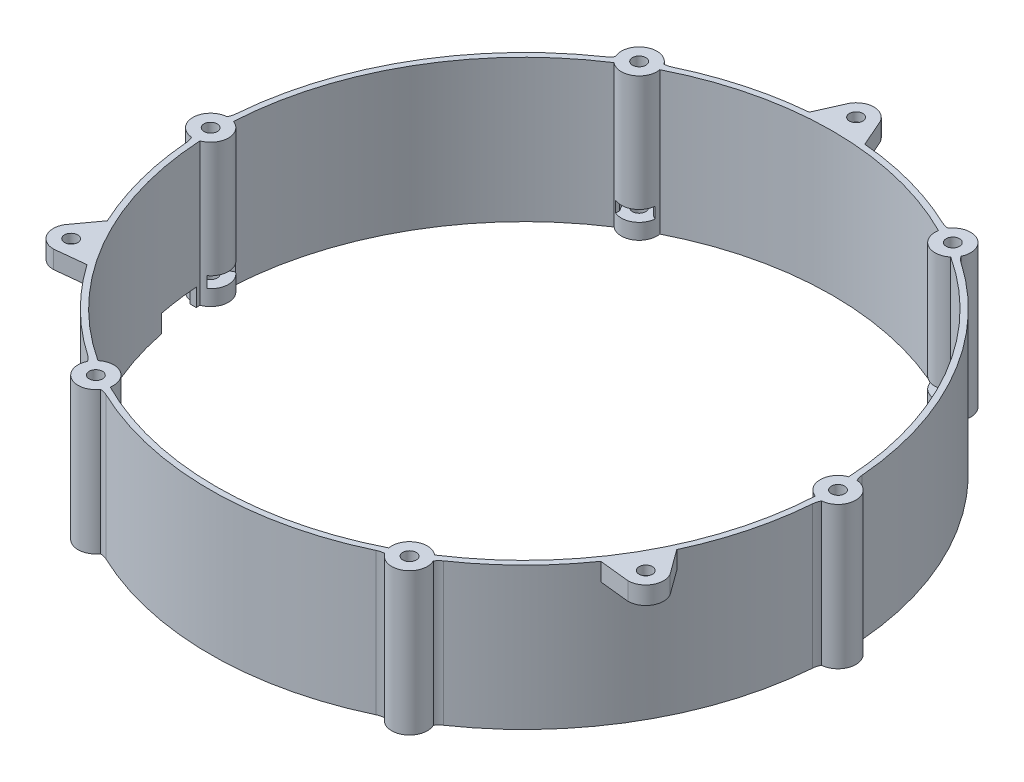
SolidWorks part; units mm, degrees
ref_plane "前视基准面" through (0, 0, 0) normal (0, 0, 1) x (1, 0, 0)
ref_plane "上视基准面" through (0, 0, 0) normal (0, 1, 0) x (1, 0, 0)
ref_plane "右视基准面" through (0, 0, 0) normal (1, 0, 0) x (0, 0, -1)
sketch "草图1" plane through (0, 0, 0) normal (0, 1, 0) x (1, 0, 0)
  line L12 (-35.25, -61.0548) -> (0, 0) construction
  line L13 (-67.3629, 4.3002) -> (-9.579, 4.3002)
  line L14 (-67.3629, -4.3002) -> (-9.579, -4.3002)
  line L15 (9.579, 4.3002) -> (67.3629, 4.3002)
  line L16 (9.579, -4.3002) -> (67.3629, -4.3002)
  line L17 (1.0654, -10.4458) -> (29.9573, -60.4881)
  line L18 (8.5136, -6.1456) -> (37.4056, -56.1878)
  line L19 (-29.9573, 60.4881) -> (-1.0654, 10.4458)
  line L20 (-37.4056, 56.1878) -> (-8.5136, 6.1456)
  line L21 (-8.5136, -6.1456) -> (-37.4056, -56.1878)
  line L22 (-1.0654, -10.4458) -> (-29.9573, -60.4881)
  line L23 (37.4056, 56.1878) -> (8.5136, 6.1456)
  line L24 (29.9573, 60.4881) -> (1.0654, 10.4458)
  line L25 (-9.579, 4.3002) -> (-67.3629, 4.3002)
  line L26 (-9.579, -4.3002) -> (-67.3629, -4.3002)
  line L27 (67.3629, -4.3002) -> (9.579, -4.3002)
  line L28 (67.3629, 4.3002) -> (9.579, 4.3002)
  line L29 (-1.0654, 10.4458) -> (-29.9573, 60.4881)
  line L30 (-8.5136, 6.1456) -> (-37.4056, 56.1878)
  line L31 (29.9573, -60.4881) -> (1.0654, -10.4458)
  line L32 (37.4056, -56.1878) -> (8.5136, -6.1456)
  line L33 (8.5136, 6.1456) -> (37.4056, 56.1878)
  line L34 (1.0654, 10.4458) -> (29.9573, 60.4881)
  line L35 (-37.4056, -56.1878) -> (-8.5136, -6.1456)
  line L36 (-29.9573, -60.4881) -> (-1.0654, -10.4458)
  line L37 (10.5, 0) -> (70.5, 0) construction
  line L38 (-10.5, 0) -> (9.5, 0) construction
  line L47 (-31.5, -54.5596) -> (-6.5, -11.2583) construction
  line L48 (-32.799, -53.8096) -> (-7.799, -10.5083)
  line L49 (-30.201, -55.3096) -> (-5.201, -12.0083)
  line L50 (-63, 0) -> (-13, 0) construction
  line L51 (-63, 1.5) -> (-13, 1.5)
  line L52 (-63, -1.5) -> (-13, -1.5)
  line L53 (-31.5, 54.5596) -> (-6.5, 11.2583) construction
  line L54 (-30.201, 55.3096) -> (-5.201, 12.0083)
  line L55 (-32.799, 53.8096) -> (-7.799, 10.5083)
  line L56 (31.5, 54.5596) -> (6.5, 11.2583) construction
  line L57 (32.799, 53.8096) -> (7.799, 10.5083)
  line L58 (30.201, 55.3096) -> (5.201, 12.0083)
  line L59 (63, 0) -> (13, 0) construction
  line L60 (63, -1.5) -> (13, -1.5)
  line L61 (63, 1.5) -> (13, 1.5)
  line L62 (31.5, -54.5596) -> (6.5, -11.2583) construction
  line L63 (30.201, -55.3096) -> (5.201, -12.0083)
  line L64 (32.799, -53.8096) -> (7.799, -10.5083)
  arc A0 (-7.8594, 1.4934) -> (-7.8594, -1.4934) centre (0, 0) ccw construction
  circle A1 centre (-8, 0) radius 1.5
  circle A2 centre (0, 8) radius 1.5
  circle A3 centre (8, 0) radius 1.5
  circle A4 centre (0, -8) radius 1.5
  arc A5 (-8.5136, 6.1456) -> (-9.579, 4.3002) centre (0, 0) ccw
  arc A6 (-67.3629, -4.3002) -> (-37.4056, -56.1878) centre (0, 0) ccw
  arc A7 (-70.5, 3) -> (-70.5, -3) centre (-70.5, 0) ccw
  circle A8 centre (-70.5, 0) radius 1.5
  arc A9 (-32.6519, 62.5548) -> (-37.8481, 59.5548) centre (-35.25, 61.0548) ccw
  circle A10 centre (-35.25, 61.0548) radius 1.5
  arc A11 (37.8481, 59.5548) -> (32.6519, 62.5548) centre (35.25, 61.0548) ccw
  circle A12 centre (35.25, 61.0548) radius 1.5
  arc A13 (70.5, -3) -> (70.5, 3) centre (70.5, 0) ccw
  circle A14 centre (70.5, 0) radius 1.5
  arc A15 (32.6519, -62.5548) -> (37.8481, -59.5548) centre (35.25, -61.0548) ccw
  circle A16 centre (35.25, -61.0548) radius 1.5
  arc A17 (-37.8481, -59.5548) -> (-32.6519, -62.5548) centre (-35.25, -61.0548) ccw
  circle A18 centre (-35.25, -61.0548) radius 1.5
  arc A21 (1.4934, 7.8594) -> (-6.746, 4.3002) centre (0, 0) ccw construction
  arc A22 (-1.4934, -7.8594) -> (1.4934, -7.8594) centre (0, 0) ccw construction
  arc A23 (7.8594, -1.4934) -> (6.746, 4.3002) centre (0, 0) ccw construction
  circle A24 centre (0, 0) radius 4.5
  arc A25 (1.0654, 10.4458) -> (-1.0654, 10.4458) centre (0, 0) ccw
  arc A26 (9.579, 4.3002) -> (8.5136, 6.1456) centre (0, 0) ccw
  arc A27 (8.5136, -6.1456) -> (9.579, -4.3002) centre (0, 0) ccw
  arc A28 (-1.0654, -10.4458) -> (1.0654, -10.4458) centre (0, 0) ccw
  arc A29 (-9.579, -4.3002) -> (-8.5136, -6.1456) centre (0, 0) ccw
  arc A30 (-37.4056, 56.1878) -> (-67.3629, 4.3002) centre (0, 0) ccw
  arc A31 (29.9573, 60.4881) -> (-29.9573, 60.4881) centre (0, 0) ccw
  arc A32 (67.3629, 4.3002) -> (37.4056, 56.1878) centre (0, 0) ccw
  arc A33 (37.4056, -56.1878) -> (67.3629, -4.3002) centre (0, 0) ccw
  arc A34 (-29.9573, -60.4881) -> (29.9573, -60.4881) centre (0, 0) ccw
  arc A35 (32.6519, 62.5548) -> (-32.6519, 62.5548) centre (0, 0) ccw
  arc A36 (70.5, 3) -> (37.8481, 59.5548) centre (0, 0) ccw
  arc A37 (37.8481, -59.5548) -> (70.5, -3) centre (0, 0) ccw
  arc A38 (-32.6519, -62.5548) -> (32.6519, -62.5548) centre (0, 0) ccw
  arc A39 (-70.5, -3) -> (-37.8481, -59.5548) centre (0, 0) ccw
  arc A40 (-37.8481, 59.5548) -> (-70.5, 3) centre (0, 0) ccw
  arc A41 (-32.799, -53.8096) -> (-30.201, -55.3096) centre (-31.5, -54.5596) ccw
  arc A42 (-5.201, -12.0083) -> (-7.799, -10.5083) centre (-6.5, -11.2583) ccw
  arc A43 (-63, 1.5) -> (-63, -1.5) centre (-63, 0) ccw
  arc A44 (-13, -1.5) -> (-13, 1.5) centre (-13, 0) ccw
  arc A45 (-30.201, 55.3096) -> (-32.799, 53.8096) centre (-31.5, 54.5596) ccw
  arc A46 (-7.799, 10.5083) -> (-5.201, 12.0083) centre (-6.5, 11.2583) ccw
  arc A47 (32.799, 53.8096) -> (30.201, 55.3096) centre (31.5, 54.5596) ccw
  arc A48 (5.201, 12.0083) -> (7.799, 10.5083) centre (6.5, 11.2583) ccw
  arc A49 (63, -1.5) -> (63, 1.5) centre (63, 0) ccw
  arc A50 (13, 1.5) -> (13, -1.5) centre (13, 0) ccw
  arc A51 (30.201, -55.3096) -> (32.799, -53.8096) centre (31.5, -54.5596) ccw
  arc A52 (7.799, -10.5083) -> (5.201, -12.0083) centre (6.5, -11.2583) ccw
  point P14 (0, 0)
  point P15 (0, 0)
  point P20 (-19, -32.909)
  point P51 (-38, 0)
  point P52 (0, 0)
  point P92 (-19, 32.909)
  point P99 (19, 32.909)
  point P106 (38, 0)
  point P111 (0, 0)
  point P130 (19, -32.909)
  point P135 (0, 0)
  dimension "D1" = 16
  dimension "D2" = 3
  dimension "D4" = 2.5
  dimension "D5" = 135
  dimension "D6" = 6
  dimension "D7" = 3
  dimension "D9" = 9
  dimension "D11" = 50
  dimension "D8" = 6
  dimension "D12" = 13
  dimension "D13" = 3
  dimension "D3" = 4
  dimension "D10" = 6
  dimension "D14" = 6
extrude "凸台-拉伸1" add sketch "草图1" along normal blind 4 contours A9 A40 A7 A39 A17 A38 A15 A37 A13 A36 A11 A35 A52 L64 A51 L63 A50 L61 A49 L60 A48 L58 A47 L57 A46 L55 A45 L54 A44 L52 A43 L51 A42 L49 A41 L48 L14 A29 L21 A6 A1 A2 region at (-59.3453, 0, -34.263)
fillet "圆角1" radius 4 24 edges at (-37.4056, 2, 56.1878) (-67.3629, 2, 4.3002) (-70.5, 2, 3) (-70.5, 2, -3) (-67.3629, 2, -4.3002) (-37.4056, 2, -56.1878) (-29.9573, 2, -60.4881) (-37.8481, 2, -59.5548) (-32.6519, 2, -62.5548) (32.6519, 2, -62.5548) (29.9573, 2, -60.4881) (37.4056, 2, -56.1878) (37.8481, 2, -59.5548) (70.5, 2, -3) (70.5, 2, 3) (67.3629, 2, -4.3002) (67.3629, 2, 4.3002) (37.8481, 2, 59.5548) (37.4056, 2, 56.1878) (32.6519, 2, 62.5548) (29.9573, 2, 60.4881) (-37.8481, 2, 59.5548) (-29.9573, 2, 60.4881) (-32.6519, 2, 62.5548)
fillet "圆角2" radius 4 12 edges at (-1.0654, 2, 10.4458) (-8.5136, 2, 6.1456) (-9.579, 2, 4.3002) (-9.579, 2, -4.3002) (-8.5136, 2, -6.1456) (1.0654, 2, -10.4458) (-1.0654, 2, -10.4458) (9.579, 2, -4.3002) (8.5136, 2, -6.1456) (9.579, 2, 4.3002) (8.5136, 2, 6.1456) (1.0654, 2, 10.4458)
sketch "草图2" plane through (0, 0, 0) normal (0, -1, 0) x (-1, 0, 0)
  line L0 (23.0864, -63.4293) -> (23.5994, -64.8388)
  line L1 (0, 0) -> (0, -46.6688) construction
  line L2 (-23.0864, -63.4293) -> (-23.5994, -64.8388)
  line L3 (-43.3882, -51.708) -> (-44.3523, -52.8571)
  line L4 (-66.4745, -11.7213) -> (-67.9517, -11.9817)
  line L5 (-66.4745, 11.7213) -> (-67.9517, 11.9817)
  line L6 (-43.3882, 51.708) -> (-44.3523, 52.8571)
  line L7 (-23.0864, 63.4293) -> (-23.5994, 64.8388)
  line L8 (23.0864, 63.4293) -> (23.5994, 64.8388)
  line L9 (43.3882, 51.708) -> (44.3523, 52.8571)
  line L10 (66.4745, 11.7213) -> (67.9517, 11.9817)
  line L11 (66.4745, -11.7213) -> (67.9517, -11.9817)
  line L12 (43.3882, -51.708) -> (44.3523, -52.8571)
  arc A0 (-23.0864, -63.4293) -> (23.0864, -63.4293) centre (0, 0) ccw
  arc A1 (-23.5994, -64.8388) -> (23.5994, -64.8388) centre (0, 0) ccw
  arc A2 (-66.4745, -11.7213) -> (-43.3882, -51.708) centre (0, 0) ccw
  arc A3 (-67.9517, -11.9817) -> (-44.3523, -52.8571) centre (0, 0) ccw
  arc A4 (-43.3882, 51.708) -> (-66.4745, 11.7213) centre (0, 0) ccw
  arc A5 (-44.3523, 52.8571) -> (-67.9517, 11.9817) centre (0, 0) ccw
  arc A6 (23.0864, 63.4293) -> (-23.0864, 63.4293) centre (0, 0) ccw
  arc A7 (23.5994, 64.8388) -> (-23.5994, 64.8388) centre (0, 0) ccw
  arc A8 (66.4745, 11.7213) -> (43.3882, 51.708) centre (0, 0) ccw
  arc A9 (67.9517, 11.9817) -> (44.3523, 52.8571) centre (0, 0) ccw
  arc A10 (43.3882, -51.708) -> (66.4745, -11.7213) centre (0, 0) ccw
  arc A11 (44.3523, -52.8571) -> (67.9517, -11.9817) centre (0, 0) ccw
  point P30 (0, 0)
  dimension "D1" = 1.5
  dimension "D2" = 20
  dimension "D3" = 6
extrude "凸台-拉伸2" add sketch "草图2" along normal blind 5
chamfer "倒角1" distance 0.5 angle 45 6 edges at (59.7558, -5, -34.5) (59.7558, -5, 34.5) (0, -5, 69) (-59.7558, -5, 34.5) (-59.7558, -5, -34.5) (0, -5, -69)
sketch "草图3" plane through (0, 0, 0) normal (0, -1, 0) x (1, 0, 0)
  arc A0 (-37.8339, 58.0014) -> (-69.1476, 3.7644) centre (0, 0) ccw
  arc A2 (-69.1476, -3.7644) -> (-37.8339, -58.0014) centre (0, 0) ccw
  arc A4 (69.1476, 3.7644) -> (69.1476, -3.7644) centre (70.5, 0) ccw
  arc A5 (69.1476, 3.7644) -> (37.8339, 58.0014) centre (0, 0) ccw
  arc A6 (37.8339, -58.0014) -> (69.1476, -3.7644) centre (0, 0) ccw
  arc A7 (-31.3137, -61.7658) -> (31.3137, -61.7658) centre (0, 0) ccw
  arc A9 (70.7964, -3.989) -> (70.7964, 3.989) centre (70.5, 0) ccw
  arc A10 (31.3137, 61.7658) -> (37.8339, 58.0014) centre (35.25, 61.0548) ccw
  arc A11 (31.3137, 61.7658) -> (-31.3137, 61.7658) centre (0, 0) ccw
  arc A12 (37.8339, -58.0014) -> (31.3137, -61.7658) centre (35.25, -61.0548) ccw
  arc A13 (-38.8528, -59.317) -> (-31.9436, -63.306) centre (-35.25, -61.0548) ccw
  arc A14 (-70.7964, 3.989) -> (-70.7964, -3.989) centre (-70.5, 0) ccw
  arc A15 (-31.9436, 63.306) -> (-38.8528, 59.317) centre (-35.25, 61.0548) ccw
  arc A16 (38.8528, 59.317) -> (31.9436, 63.306) centre (35.25, 61.0548) ccw
  arc A17 (-37.8339, 58.0014) -> (-31.3137, 61.7658) centre (-35.25, 61.0548) ccw
  arc A18 (-69.1476, -3.7644) -> (-69.1476, 3.7644) centre (-70.5, 0) ccw
  arc A19 (-31.3137, -61.7658) -> (-37.8339, -58.0014) centre (-35.25, -61.0548) ccw
  arc A20 (31.9436, -63.306) -> (38.8528, -59.317) centre (35.25, -61.0548) ccw
  circle A21 centre (70.5, 0) radius 1.5
  circle A22 centre (35.25, 61.0548) radius 1.5
  circle A23 centre (-35.25, 61.0548) radius 1.5
  arc A24 (-38.2453, -61.2225) -> (-33.8976, -63.7327) centre (-35.25, -61.0548) ccw
  arc A25 (-30.3726, -63.6926) -> (-33.8976, -63.7327) centre (-32.0944, -67.3031) ccw
  arc A26 (-30.3726, -63.6926) -> (30.3726, -63.6926) centre (0, 0) ccw
  arc A27 (33.8976, -63.7327) -> (30.3726, -63.6926) centre (32.0944, -67.3031) ccw
  arc A28 (33.8976, -63.7327) -> (38.2453, -61.2225) centre (35.25, -61.0548) ccw
  arc A29 (39.9731, -58.1498) -> (38.2453, -61.2225) centre (42.2391, -61.4461) ccw
  arc A30 (39.9731, -58.1498) -> (70.3458, -5.5428) centre (0, 0) ccw
  arc A31 (72.1429, -2.5102) -> (70.3458, -5.5428) centre (74.3334, -5.857) ccw
  arc A32 (72.1429, -2.5102) -> (72.1429, 2.5102) centre (70.5, 0) ccw
  arc A33 (70.3458, 5.5428) -> (72.1429, 2.5102) centre (74.3334, 5.857) ccw
  arc A34 (70.3458, 5.5428) -> (39.9731, 58.1498) centre (0, 0) ccw
  arc A35 (38.2453, 61.2225) -> (39.9731, 58.1498) centre (42.2391, 61.4461) ccw
  arc A36 (38.2453, 61.2225) -> (33.8976, 63.7327) centre (35.25, 61.0548) ccw
  arc A37 (30.3726, 63.6926) -> (33.8976, 63.7327) centre (32.0944, 67.3031) ccw
  arc A38 (30.3726, 63.6926) -> (-30.3726, 63.6926) centre (0, 0) ccw
  arc A39 (-33.8976, 63.7327) -> (-30.3726, 63.6926) centre (-32.0944, 67.3031) ccw
  arc A40 (-33.8976, 63.7327) -> (-38.2453, 61.2225) centre (-35.25, 61.0548) ccw
  arc A41 (-39.9731, 58.1498) -> (-38.2453, 61.2225) centre (-42.2391, 61.4461) ccw
  arc A42 (-39.9731, 58.1498) -> (-70.3458, 5.5428) centre (0, 0) ccw
  arc A43 (-72.1429, 2.5102) -> (-70.3458, 5.5428) centre (-74.3334, 5.857) ccw
  arc A44 (-72.1429, 2.5102) -> (-72.1429, -2.5102) centre (-70.5, 0) ccw
  arc A45 (-70.3458, -5.5428) -> (-72.1429, -2.5102) centre (-74.3334, -5.857) ccw
  arc A46 (-70.3458, -5.5428) -> (-39.9731, -58.1498) centre (0, 0) ccw
  arc A47 (-38.2453, -61.2225) -> (-39.9731, -58.1498) centre (-42.2391, -61.4461) ccw
  arc A49 (-30.3726, -63.6926) -> (-31.9436, -63.306) centre (-32.0944, -67.3031) ccw
  arc A50 (-30.3726, -63.6926) -> (30.3726, -63.6926) centre (0, 0) ccw
  arc A51 (31.9436, -63.306) -> (30.3726, -63.6926) centre (32.0944, -67.3031) ccw
  arc A53 (39.9731, -58.1498) -> (38.8528, -59.317) centre (42.2391, -61.4461) ccw
  arc A54 (39.9731, -58.1498) -> (70.3458, -5.5428) centre (0, 0) ccw
  arc A55 (70.7964, -3.989) -> (70.3458, -5.5428) centre (74.3334, -5.857) ccw
  arc A57 (70.3458, 5.5428) -> (70.7964, 3.989) centre (74.3334, 5.857) ccw
  arc A58 (70.3458, 5.5428) -> (39.9731, 58.1498) centre (0, 0) ccw
  arc A59 (38.8528, 59.317) -> (39.9731, 58.1498) centre (42.2391, 61.4461) ccw
  arc A61 (30.3726, 63.6926) -> (31.9436, 63.306) centre (32.0944, 67.3031) ccw
  arc A62 (30.3726, 63.6926) -> (-30.3726, 63.6926) centre (0, 0) ccw
  arc A63 (-31.9436, 63.306) -> (-30.3726, 63.6926) centre (-32.0944, 67.3031) ccw
  arc A65 (-39.9731, 58.1498) -> (-38.8528, 59.317) centre (-42.2391, 61.4461) ccw
  arc A66 (-39.9731, 58.1498) -> (-70.3458, 5.5428) centre (0, 0) ccw
  arc A67 (-70.7964, 3.989) -> (-70.3458, 5.5428) centre (-74.3334, 5.857) ccw
  arc A69 (-70.3458, -5.5428) -> (-70.7964, -3.989) centre (-74.3334, -5.857) ccw
  arc A70 (-70.3458, -5.5428) -> (-39.9731, -58.1498) centre (0, 0) ccw
  arc A71 (-38.8528, -59.317) -> (-39.9731, -58.1498) centre (-42.2391, -61.4461) ccw
  circle A73 centre (-70.5, 0) radius 1.5
  circle A74 centre (-35.25, -61.0548) radius 1.5
  circle A75 centre (35.25, -61.0548) radius 1.5
  point P57 (0, 0)
  point P80 (0, 0)
  dimension "D2" = 138.5
  dimension "D5" = 8
  dimension "D4" = 6
  dimension "D1" = 0
extrude "凸台-拉伸3" add sketch "草图3" along normal blind 10 from offset 10 separate body
sketch "草图4" plane through (0, 0, 0) normal (0, -1, 0) x (-1, 0, 0)
  line L1 (113.8553, 88.8529) -> (-113.8553, 88.8529)
  line L2 (113.8553, 88.8529) -> (113.8553, -88.8529)
  line L3 (113.8553, -88.8529) -> (-113.8553, -88.8529)
  line L4 (-113.8553, 88.8529) -> (-113.8553, -88.8529)
  line L5 (113.8553, 88.8529) -> (-113.8553, -88.8529) construction
  line L6 (113.8553, -88.8529) -> (-113.8553, 88.8529) construction
  point P0 (0, 0)
extrude "切除-拉伸1" cut sketch "草图4" against normal blind 10 and the other way blind 7
sketch "草图5" plane through (0, -10, 0) normal (0, 1, 0) x (1, 0, 0)
  line L2 (-32.0168, 61.0548) -> (-33.6334, 63.8548)
  line L3 (-33.6334, 63.8548) -> (-36.8666, 63.8548)
  line L4 (-36.8666, 63.8548) -> (-38.4832, 61.0548)
  line L5 (-38.4832, 61.0548) -> (-36.8666, 58.2548)
  line L7 (36.8666, 58.2548) -> (38.4832, 61.0548)
  line L8 (38.4832, 61.0548) -> (36.8666, 63.8548)
  line L9 (36.8666, 63.8548) -> (33.6334, 63.8548)
  line L10 (33.6334, 63.8548) -> (32.0168, 61.0548)
  line L13 (68.8834, -2.8) -> (72.1166, -2.8)
  line L14 (72.1166, -2.8) -> (73.7332, 0)
  line L15 (73.7332, 0) -> (72.1166, 2.8)
  line L16 (72.1166, 2.8) -> (68.8834, 2.8)
  line L19 (32.0168, -61.0548) -> (33.6334, -63.8548)
  line L20 (33.6334, -63.8548) -> (36.8666, -63.8548)
  line L21 (36.8666, -63.8548) -> (38.4832, -61.0548)
  line L22 (38.4832, -61.0548) -> (36.8666, -58.2548)
  line L25 (-36.8666, -58.2548) -> (-38.4832, -61.0548)
  line L26 (-38.4832, -61.0548) -> (-36.8666, -63.8548)
  line L27 (-36.8666, -63.8548) -> (-33.6334, -63.8548)
  line L28 (-33.6334, -63.8548) -> (-32.0168, -61.0548)
  line L31 (-68.8834, 2.8) -> (-72.1166, 2.8)
  line L32 (-72.1166, 2.8) -> (-73.7332, 0)
  line L33 (-73.7332, 0) -> (-72.1166, -2.8)
  line L34 (-72.1166, -2.8) -> (-68.8834, -2.8)
  line L36 (-36.8666, 58.2548) -> (-36.8666, 57.396)
  line L37 (32.0168, 61.0548) -> (31.2731, 60.6254)
  line L38 (-32.0168, 61.0548) -> (-31.2731, 60.6254)
  line L39 (-32.8251, 59.6548) -> (-32.0168, 61.0548) [skipped]
  line L40 (-36.8666, 58.2548) -> (-35.25, 58.2548) [skipped]
  line L41 (36.8666, 58.2548) -> (36.8666, 57.396)
  line L42 (68.8834, 2.8) -> (68.1397, 3.2294)
  line L43 (68.8834, -2.8) -> (68.1397, -3.2294)
  line L44 (36.8666, -58.2548) -> (36.8666, -57.396)
  line L45 (32.0168, -61.0548) -> (31.2731, -60.6254)
  line L46 (-32.0168, -61.0548) -> (-31.2731, -60.6254)
  line L47 (-36.8666, -58.2548) -> (-36.8666, -57.396)
  line L48 (-68.8834, -2.8) -> (-68.1397, -3.2294)
  line L49 (-68.8834, 2.8) -> (-68.1397, 3.2294)
  arc A0 (-32.8251, 62.4548) -> (-37.6749, 59.6548) centre (-35.25, 61.0548) ccw construction
  arc A1 (-37.8339, 58.0014) -> (-31.3137, 61.7658) centre (-35.25, 61.0548) ccw construction
  arc A2 (-37.8339, 58.0014) -> (-69.1476, 3.7644) centre (0, 0) ccw construction
  arc A3 (-69.1476, -3.7644) -> (-69.1476, 3.7644) centre (-70.5, 0) ccw construction
  arc A4 (-69.1476, -3.7644) -> (-37.8339, -58.0014) centre (0, 0) ccw construction
  arc A5 (-31.3137, -61.7658) -> (-37.8339, -58.0014) centre (-35.25, -61.0548) ccw construction
  arc A6 (-31.3137, -61.7658) -> (31.3137, -61.7658) centre (0, 0) ccw construction
  arc A7 (37.8339, -58.0014) -> (31.3137, -61.7658) centre (35.25, -61.0548) ccw construction
  arc A8 (37.8339, -58.0014) -> (69.1476, -3.7644) centre (0, 0) ccw construction
  arc A9 (69.1476, 3.7644) -> (69.1476, -3.7644) centre (70.5, 0) ccw construction
  arc A10 (69.1476, 3.7644) -> (37.8339, 58.0014) centre (0, 0) ccw construction
  arc A11 (31.3137, 61.7658) -> (37.8339, 58.0014) centre (35.25, 61.0548) ccw construction
  arc A12 (31.3137, 61.7658) -> (-31.3137, 61.7658) centre (0, 0) ccw construction
  arc A13 (-37.8339, 58.0014) -> (-36.8666, 57.396) centre (-35.25, 61.0548) ccw
  arc A14 (-37.8339, 58.0014) -> (-69.1476, 3.7644) centre (0, 0) ccw
  arc A15 (-69.1476, -3.7644) -> (-68.1397, -3.2294) centre (-70.5, 0) ccw
  arc A16 (-69.1476, -3.7644) -> (-37.8339, -58.0014) centre (0, 0) ccw
  arc A17 (-31.3137, -61.7658) -> (-31.2731, -60.6254) centre (-35.25, -61.0548) ccw
  arc A18 (-31.3137, -61.7658) -> (31.3137, -61.7658) centre (0, 0) ccw
  arc A19 (37.8339, -58.0014) -> (36.8666, -57.396) centre (35.25, -61.0548) ccw
  arc A20 (37.8339, -58.0014) -> (69.1476, -3.7644) centre (0, 0) ccw
  arc A21 (69.1476, 3.7644) -> (68.1397, 3.2294) centre (70.5, 0) ccw
  arc A22 (69.1476, 3.7644) -> (37.8339, 58.0014) centre (0, 0) ccw
  arc A23 (31.3137, 61.7658) -> (31.2731, 60.6254) centre (35.25, 61.0548) ccw
  arc A24 (31.3137, 61.7658) -> (-31.3137, 61.7658) centre (0, 0) ccw
  arc A25 (30.3726, 63.6926) -> (-30.3726, 63.6926) centre (0, 0) ccw
  arc A26 (-31.9436, 63.306) -> (-30.3726, 63.6926) centre (-32.0944, 67.3031) ccw
  arc A27 (-31.9436, 63.306) -> (-38.8528, 59.317) centre (-35.25, 61.0548) ccw
  arc A28 (-39.9731, 58.1498) -> (-38.8528, 59.317) centre (-42.2391, 61.4461) ccw
  arc A29 (-39.9731, 58.1498) -> (-70.3458, 5.5428) centre (0, 0) ccw
  arc A30 (-70.7964, 3.989) -> (-70.3458, 5.5428) centre (-74.3334, 5.857) ccw
  arc A31 (-70.7964, 3.989) -> (-70.7964, -3.989) centre (-70.5, 0) ccw
  arc A32 (-70.3458, -5.5428) -> (-70.7964, -3.989) centre (-74.3334, -5.857) ccw
  arc A33 (-70.3458, -5.5428) -> (-39.9731, -58.1498) centre (0, 0) ccw
  arc A34 (-38.8528, -59.317) -> (-39.9731, -58.1498) centre (-42.2391, -61.4461) ccw
  arc A35 (-38.8528, -59.317) -> (-31.9436, -63.306) centre (-35.25, -61.0548) ccw
  arc A36 (-30.3726, -63.6926) -> (-31.9436, -63.306) centre (-32.0944, -67.3031) ccw
  arc A37 (-30.3726, -63.6926) -> (30.3726, -63.6926) centre (0, 0) ccw
  arc A38 (31.9436, -63.306) -> (30.3726, -63.6926) centre (32.0944, -67.3031) ccw
  arc A39 (31.9436, -63.306) -> (38.8528, -59.317) centre (35.25, -61.0548) ccw
  arc A40 (39.9731, -58.1498) -> (38.8528, -59.317) centre (42.2391, -61.4461) ccw
  arc A41 (39.9731, -58.1498) -> (70.3458, -5.5428) centre (0, 0) ccw
  arc A42 (70.7964, -3.989) -> (70.3458, -5.5428) centre (74.3334, -5.857) ccw
  arc A43 (70.7964, -3.989) -> (70.7964, 3.989) centre (70.5, 0) ccw
  arc A44 (70.3458, 5.5428) -> (70.7964, 3.989) centre (74.3334, 5.857) ccw
  arc A45 (70.3458, 5.5428) -> (39.9731, 58.1498) centre (0, 0) ccw
  arc A46 (38.8528, 59.317) -> (39.9731, 58.1498) centre (42.2391, 61.4461) ccw
  arc A47 (38.8528, 59.317) -> (31.9436, 63.306) centre (35.25, 61.0548) ccw
  arc A48 (30.3726, 63.6926) -> (31.9436, 63.306) centre (32.0944, 67.3031) ccw
  arc A49 (30.3726, 63.6926) -> (-30.3726, 63.6926) centre (0, 0) ccw
  arc A50 (-31.9436, 63.306) -> (-30.3726, 63.6926) centre (-32.0944, 67.3031) ccw
  arc A51 (-31.9436, 63.306) -> (-38.8528, 59.317) centre (-35.25, 61.0548) ccw
  arc A52 (-39.9731, 58.1498) -> (-38.8528, 59.317) centre (-42.2391, 61.4461) ccw
  arc A53 (-39.9731, 58.1498) -> (-70.3458, 5.5428) centre (0, 0) ccw
  arc A54 (-70.7964, 3.989) -> (-70.3458, 5.5428) centre (-74.3334, 5.857) ccw
  arc A55 (-70.7964, 3.989) -> (-70.7964, -3.989) centre (-70.5, 0) ccw
  arc A56 (-70.3458, -5.5428) -> (-70.7964, -3.989) centre (-74.3334, -5.857) ccw
  arc A57 (-70.3458, -5.5428) -> (-39.9731, -58.1498) centre (0, 0) ccw
  arc A58 (-38.8528, -59.317) -> (-39.9731, -58.1498) centre (-42.2391, -61.4461) ccw
  arc A59 (-38.8528, -59.317) -> (-31.9436, -63.306) centre (-35.25, -61.0548) ccw
  arc A60 (-30.3726, -63.6926) -> (-31.9436, -63.306) centre (-32.0944, -67.3031) ccw
  arc A61 (-30.3726, -63.6926) -> (30.3726, -63.6926) centre (0, 0) ccw
  arc A62 (31.9436, -63.306) -> (30.3726, -63.6926) centre (32.0944, -67.3031) ccw
  arc A63 (31.9436, -63.306) -> (38.8528, -59.317) centre (35.25, -61.0548) ccw
  arc A64 (39.9731, -58.1498) -> (38.8528, -59.317) centre (42.2391, -61.4461) ccw
  arc A65 (39.9731, -58.1498) -> (70.3458, -5.5428) centre (0, 0) ccw
  arc A66 (70.7964, -3.989) -> (70.3458, -5.5428) centre (74.3334, -5.857) ccw
  arc A67 (70.7964, -3.989) -> (70.7964, 3.989) centre (70.5, 0) ccw
  arc A68 (70.3458, 5.5428) -> (70.7964, 3.989) centre (74.3334, 5.857) ccw
  arc A69 (70.3458, 5.5428) -> (39.9731, 58.1498) centre (0, 0) ccw
  arc A70 (38.8528, 59.317) -> (39.9731, 58.1498) centre (42.2391, 61.4461) ccw
  arc A71 (38.8528, 59.317) -> (31.9436, 63.306) centre (35.25, 61.0548) ccw
  arc A72 (30.3726, 63.6926) -> (31.9436, 63.306) centre (32.0944, 67.3031) ccw
  arc A73 (-31.2731, 60.6254) -> (-31.3137, 61.7658) centre (-35.25, 61.0548) ccw
  arc A74 (36.8666, 57.396) -> (37.8339, 58.0014) centre (35.25, 61.0548) ccw
  arc A75 (68.1397, -3.2294) -> (69.1476, -3.7644) centre (70.5, 0) ccw
  arc A76 (31.2731, -60.6254) -> (31.3137, -61.7658) centre (35.25, -61.0548) ccw
  arc A77 (-36.8666, -57.396) -> (-37.8339, -58.0014) centre (-35.25, -61.0548) ccw
  arc A78 (-68.1397, 3.2294) -> (-69.1476, 3.7644) centre (-70.5, 0) ccw
  point P42 (0, 0)
  point P141 (0, 0)
  dimension "D1" = 5.6
  dimension "D4" = 6
  dimension "D3" = 0
  dimension "D2" = 6
extrude "凸台-拉伸4" add sketch "草图5" along normal blind 2.5
sketch "草图7" plane through (0, -20, 0) normal (0, -1, 0) x (-1, 0, 0)
  circle A0 centre (0, 0) radius 85.197
extrude "切除-拉伸2" cut sketch "草图7" against normal blind 6.5
sketch "草图8" plane through (0, -7.5, 0) normal (0, 1, 0) x (1, 0, 0)
  circle A0 centre (-35.25, 61.0548) radius 1.5
  arc A1 (-37.8339, 58.0014) -> (-31.3137, 61.7658) centre (-35.25, 61.0548) ccw
  arc A2 (-31.9436, 63.306) -> (-38.8528, 59.317) centre (-35.25, 61.0548) ccw construction
  arc A3 (-31.9436, 63.306) -> (-38.8528, 59.317) centre (-35.25, 61.0548) ccw
  arc A4 (31.3137, 61.7658) -> (-31.3137, 61.7658) centre (0, 0) ccw construction
  arc A5 (-37.8339, 58.0014) -> (-69.1476, 3.7644) centre (0, 0) ccw construction
  arc A6 (31.3137, 61.7658) -> (-31.3137, 61.7658) centre (0, 0) ccw
  arc A7 (-37.8339, 58.0014) -> (-69.1476, 3.7644) centre (0, 0) ccw
  circle A8 centre (35.25, 61.0548) radius 1.5
  arc A9 (31.3137, 61.7658) -> (37.8339, 58.0014) centre (35.25, 61.0548) ccw
  arc A10 (69.1476, 3.7644) -> (37.8339, 58.0014) centre (0, 0) ccw
  arc A11 (31.3137, 61.7658) -> (-31.3137, 61.7658) centre (0, 0) ccw
  circle A12 centre (70.5, 0) radius 1.5
  arc A13 (69.1476, 3.7644) -> (69.1476, -3.7644) centre (70.5, 0) ccw
  arc A14 (37.8339, -58.0014) -> (69.1476, -3.7644) centre (0, 0) ccw
  arc A15 (69.1476, 3.7644) -> (37.8339, 58.0014) centre (0, 0) ccw
  circle A16 centre (35.25, -61.0548) radius 1.5
  arc A17 (37.8339, -58.0014) -> (31.3137, -61.7658) centre (35.25, -61.0548) ccw
  arc A18 (-31.3137, -61.7658) -> (31.3137, -61.7658) centre (0, 0) ccw
  arc A19 (37.8339, -58.0014) -> (69.1476, -3.7644) centre (0, 0) ccw
  circle A20 centre (-35.25, -61.0548) radius 1.5
  arc A21 (-31.3137, -61.7658) -> (-37.8339, -58.0014) centre (-35.25, -61.0548) ccw
  arc A22 (-69.1476, -3.7644) -> (-37.8339, -58.0014) centre (0, 0) ccw
  arc A23 (-31.3137, -61.7658) -> (31.3137, -61.7658) centre (0, 0) ccw
  arc A24 (30.3726, 63.6926) -> (31.9436, 63.306) centre (32.0944, 67.3031) ccw
  arc A25 (30.3726, 63.6926) -> (-30.3726, 63.6926) centre (0, 0) ccw
  arc A26 (-31.9436, 63.306) -> (-30.3726, 63.6926) centre (-32.0944, 67.3031) ccw
  arc A27 (-31.9436, 63.306) -> (-38.8528, 59.317) centre (-35.25, 61.0548) ccw
  arc A28 (-39.9731, 58.1498) -> (-38.8528, 59.317) centre (-42.2391, 61.4461) ccw
  arc A29 (-39.9731, 58.1498) -> (-70.3458, 5.5428) centre (0, 0) ccw
  arc A30 (-70.7964, 3.989) -> (-70.3458, 5.5428) centre (-74.3334, 5.857) ccw
  arc A31 (-70.7964, 3.989) -> (-70.7964, -3.989) centre (-70.5, 0) ccw
  arc A32 (-70.3458, -5.5428) -> (-70.7964, -3.989) centre (-74.3334, -5.857) ccw
  arc A33 (-70.3458, -5.5428) -> (-39.9731, -58.1498) centre (0, 0) ccw
  arc A34 (-38.8528, -59.317) -> (-39.9731, -58.1498) centre (-42.2391, -61.4461) ccw
  arc A35 (-38.8528, -59.317) -> (-31.9436, -63.306) centre (-35.25, -61.0548) ccw
  arc A36 (-30.3726, -63.6926) -> (-31.9436, -63.306) centre (-32.0944, -67.3031) ccw
  arc A37 (-30.3726, -63.6926) -> (30.3726, -63.6926) centre (0, 0) ccw
  arc A38 (31.9436, -63.306) -> (30.3726, -63.6926) centre (32.0944, -67.3031) ccw
  arc A39 (31.9436, -63.306) -> (38.8528, -59.317) centre (35.25, -61.0548) ccw
  arc A40 (39.9731, -58.1498) -> (38.8528, -59.317) centre (42.2391, -61.4461) ccw
  arc A41 (39.9731, -58.1498) -> (70.3458, -5.5428) centre (0, 0) ccw
  arc A42 (70.7964, -3.989) -> (70.3458, -5.5428) centre (74.3334, -5.857) ccw
  arc A43 (70.7964, -3.989) -> (70.7964, 3.989) centre (70.5, 0) ccw
  arc A44 (70.3458, 5.5428) -> (70.7964, 3.989) centre (74.3334, 5.857) ccw
  arc A45 (70.3458, 5.5428) -> (39.9731, 58.1498) centre (0, 0) ccw
  arc A46 (38.8528, 59.317) -> (39.9731, 58.1498) centre (42.2391, 61.4461) ccw
  arc A47 (38.8528, 59.317) -> (31.9436, 63.306) centre (35.25, 61.0548) ccw
  arc A48 (30.3726, 63.6926) -> (31.9436, 63.306) centre (32.0944, 67.3031) ccw
  arc A49 (30.3726, 63.6926) -> (-30.3726, 63.6926) centre (0, 0) ccw
  arc A50 (-31.9436, 63.306) -> (-30.3726, 63.6926) centre (-32.0944, 67.3031) ccw
  arc A52 (-39.9731, 58.1498) -> (-38.8528, 59.317) centre (-42.2391, 61.4461) ccw
  arc A53 (-39.9731, 58.1498) -> (-70.3458, 5.5428) centre (0, 0) ccw
  arc A54 (-70.7964, 3.989) -> (-70.3458, 5.5428) centre (-74.3334, 5.857) ccw
  arc A55 (-70.7964, 3.989) -> (-70.7964, -3.989) centre (-70.5, 0) ccw
  arc A56 (-70.3458, -5.5428) -> (-70.7964, -3.989) centre (-74.3334, -5.857) ccw
  arc A57 (-70.3458, -5.5428) -> (-39.9731, -58.1498) centre (0, 0) ccw
  arc A58 (-38.8528, -59.317) -> (-39.9731, -58.1498) centre (-42.2391, -61.4461) ccw
  arc A59 (-38.8528, -59.317) -> (-31.9436, -63.306) centre (-35.25, -61.0548) ccw
  arc A60 (-30.3726, -63.6926) -> (-31.9436, -63.306) centre (-32.0944, -67.3031) ccw
  arc A61 (-30.3726, -63.6926) -> (30.3726, -63.6926) centre (0, 0) ccw
  arc A62 (31.9436, -63.306) -> (30.3726, -63.6926) centre (32.0944, -67.3031) ccw
  arc A63 (31.9436, -63.306) -> (38.8528, -59.317) centre (35.25, -61.0548) ccw
  arc A64 (39.9731, -58.1498) -> (38.8528, -59.317) centre (42.2391, -61.4461) ccw
  arc A65 (39.9731, -58.1498) -> (70.3458, -5.5428) centre (0, 0) ccw
  arc A66 (70.7964, -3.989) -> (70.3458, -5.5428) centre (74.3334, -5.857) ccw
  arc A67 (70.7964, -3.989) -> (70.7964, 3.989) centre (70.5, 0) ccw
  arc A68 (70.3458, 5.5428) -> (70.7964, 3.989) centre (74.3334, 5.857) ccw
  arc A69 (70.3458, 5.5428) -> (39.9731, 58.1498) centre (0, 0) ccw
  arc A70 (38.8528, 59.317) -> (39.9731, 58.1498) centre (42.2391, 61.4461) ccw
  arc A71 (38.8528, 59.317) -> (31.9436, 63.306) centre (35.25, 61.0548) ccw
  circle A72 centre (-70.5, 0) radius 1.5
  arc A73 (-69.1476, -3.7644) -> (-69.1476, 3.7644) centre (-70.5, 0) ccw
  arc A74 (-37.8339, 58.0014) -> (-69.1476, 3.7644) centre (0, 0) ccw
  arc A75 (-69.1476, -3.7644) -> (-37.8339, -58.0014) centre (0, 0) ccw
  point P89 (0, 0)
  dimension "D2" = 6
  dimension "D1" = 0
extrude "凸台-拉伸5" add sketch "草图8" along normal blind 26 contours A70 A71 A48 A49 A50 A3 A52 A53 A54 A55 A56 A57 A58 A59 A60 A61 A62 A63 A64 A65 A66 A67 A68 A69 A72 A0 A8 A12 A16 A20 A22 A73 A7 A1 A6 A9 A10 A13 A14 A17 A18 A21 region at (-31.0893, -7.5, -63.2198)
sketch "草图10" plane through (0, -13.5, 0) normal (0, -1, 0) x (-1, 0, 0)
  line L1 (-64.5741, -41.2819) -> (-57.7443, -40.5566)
  line L2 (-68.0382, -35.2819) -> (-63.9953, -29.7297)
  line L4 (-3.4641, 76.5638) -> (-6.2509, 70.2864)
  line L5 (3.4641, 76.5638) -> (6.2509, 70.2864)
  line L8 (68.0382, -35.2819) -> (63.9953, -29.7297)
  line L9 (64.5741, -41.2819) -> (57.7443, -40.5566)
  line L12 (3.4641, -76.5638) -> (6.2509, -70.2864) [skipped]
  line L13 (-3.4641, -76.5638) -> (-6.2509, -70.2864) [skipped]
  line L14 (64.5741, 41.2819) -> (57.7443, 40.5566) [skipped]
  line L15 (68.0382, 35.2819) -> (63.9953, 29.7297) [skipped]
  line L16 (-68.0382, 35.2819) -> (-63.9953, 29.7297) [skipped]
  line L17 (-64.5741, 41.2819) -> (-57.7443, 40.5566) [skipped]
  arc A2 (-68.0382, -35.2819) -> (-64.5741, -41.2819) centre (-64.5741, -37.2819) ccw
  arc A3 (-70.3458, -5.5428) -> (-39.9731, -58.1498) centre (0, 0) ccw construction
  circle A4 centre (-64.5741, -37.2819) radius 1.5
  arc A5 (-63.9953, -29.7297) -> (-57.7443, -40.5566) centre (0, 0) ccw
  arc A9 (3.4641, 76.5638) -> (-3.4641, 76.5638) centre (0, 74.5638) ccw
  circle A10 centre (0, 74.5638) radius 1.5
  arc A11 (6.2509, 70.2864) -> (-6.2509, 70.2864) centre (0, 0) ccw
  arc A15 (64.5741, -41.2819) -> (68.0382, -35.2819) centre (64.5741, -37.2819) ccw
  circle A16 centre (64.5741, -37.2819) radius 1.5
  arc A17 (57.7443, -40.5566) -> (63.9953, -29.7297) centre (0, 0) ccw
  arc A21 (-3.4641, -76.5638) -> (3.4641, -76.5638) centre (0, -74.5638) ccw [skipped]
  circle A22 centre (0, -74.5638) radius 1.5 [skipped]
  arc A23 (-6.2509, -70.2864) -> (6.2509, -70.2864) centre (0, 0) ccw [skipped]
  arc A24 (68.0382, 35.2819) -> (64.5741, 41.2819) centre (64.5741, 37.2819) ccw [skipped]
  circle A25 centre (64.5741, 37.2819) radius 1.5 [skipped]
  arc A26 (63.9953, 29.7297) -> (57.7443, 40.5566) centre (0, 0) ccw [skipped]
  arc A27 (-64.5741, 41.2819) -> (-68.0382, 35.2819) centre (-64.5741, 37.2819) ccw [skipped]
  circle A28 centre (-64.5741, 37.2819) radius 1.5 [skipped]
  arc A29 (-57.7443, 40.5566) -> (-63.9953, 29.7297) centre (0, 0) ccw [skipped]
  point P43 (0, 0)
  dimension "D1" = 8
  dimension "D2" = 3
  dimension "D3" = 6
extrude "凸台-拉伸6" add sketch "草图10" against normal blind 4 from offset 28 offset against normal yes
sketch "草图12" plane through (0, 14.5, 0) normal (0, -1, 0) x (1, 0, 0)
  line L1 (-67.3741, 38.8985) -> (-67.3741, 35.6653)
  line L2 (-67.3741, 35.6653) -> (-64.5741, 34.0487)
  line L3 (-64.5741, 34.0487) -> (-61.7741, 35.6653)
  line L4 (-61.7741, 35.6653) -> (-61.7741, 38.8985)
  line L5 (-61.7741, 38.8985) -> (-64.5741, 40.5151)
  line L6 (-64.5741, 40.5151) -> (-67.3741, 38.8985)
  line L12 (67.3741, 38.8985) -> (64.5741, 40.5151)
  line L13 (64.5741, 40.5151) -> (61.7741, 38.8985)
  line L14 (61.7741, 38.8985) -> (61.7741, 35.6653)
  line L15 (61.7741, 35.6653) -> (64.5741, 34.0487)
  line L16 (64.5741, 34.0487) -> (67.3741, 35.6653)
  line L17 (67.3741, 35.6653) -> (67.3741, 38.8985)
  line L24 (0, -77.797) -> (2.8, -76.1804)
  line L25 (2.8, -76.1804) -> (2.8, -72.9472)
  line L26 (2.8, -72.9472) -> (0, -71.3306)
  line L27 (0, -71.3306) -> (-2.8, -72.9472)
  line L28 (-2.8, -72.9472) -> (-2.8, -76.1804)
  line L29 (-2.8, -76.1804) -> (0, -77.797)
  line L36 (0, 77.797) -> (-2.8, 76.1804) [skipped]
  line L37 (-2.8, 76.1804) -> (-2.8, 72.9472) [skipped]
  line L38 (-2.8, 72.9472) -> (0, 71.3306) [skipped]
  line L39 (0, 71.3306) -> (2.8, 72.9472) [skipped]
  line L40 (2.8, 72.9472) -> (2.8, 76.1804) [skipped]
  line L41 (2.8, 76.1804) -> (0, 77.797) [skipped]
  line L42 (67.3741, -38.8985) -> (67.3741, -35.6653) [skipped]
  line L43 (67.3741, -35.6653) -> (64.5741, -34.0487) [skipped]
  line L44 (64.5741, -34.0487) -> (61.7741, -35.6653) [skipped]
  line L45 (61.7741, -35.6653) -> (61.7741, -38.8985) [skipped]
  line L46 (61.7741, -38.8985) -> (64.5741, -40.5151) [skipped]
  line L47 (64.5741, -40.5151) -> (67.3741, -38.8985) [skipped]
  line L48 (-67.3741, -38.8985) -> (-64.5741, -40.5151) [skipped]
  line L49 (-64.5741, -40.5151) -> (-61.7741, -38.8985) [skipped]
  line L50 (-61.7741, -38.8985) -> (-61.7741, -35.6653) [skipped]
  line L51 (-61.7741, -35.6653) -> (-64.5741, -34.0487) [skipped]
  line L52 (-64.5741, -34.0487) -> (-67.3741, -35.6653) [skipped]
  line L53 (-67.3741, -35.6653) -> (-67.3741, -38.8985) [skipped]
  circle A0 centre (-64.5741, 37.2819) radius 2.8 construction
  point P41 (0, 0)
  dimension "D1" = 5.6
  dimension "D2" = 6
extrude "切除-拉伸3" cut sketch "草图12" against normal blind 2
sketch "草图13" plane through (0, -13.5, 0) normal (0, -1, 0) x (-1, 0, 0)
  line L1 (81.743, -13.6327) -> (64.2734, -13.6327)
  line L2 (81.743, -13.6327) -> (81.743, -4.6327)
  line L3 (81.743, -4.6327) -> (64.2734, -4.6327)
  line L4 (64.2734, -13.6327) -> (64.2734, -4.6327)
  line L5 (81.743, -13.6327) -> (64.2734, -4.6327) construction
  line L6 (81.743, -4.6327) -> (64.2734, -13.6327) construction
  point P0 (73.0082, -9.1327)
  point P5 (73.0082, -9.1327)
  dimension "D1" = 9
extrude "切除-拉伸4" cut sketch "草图13" against normal blind 4
